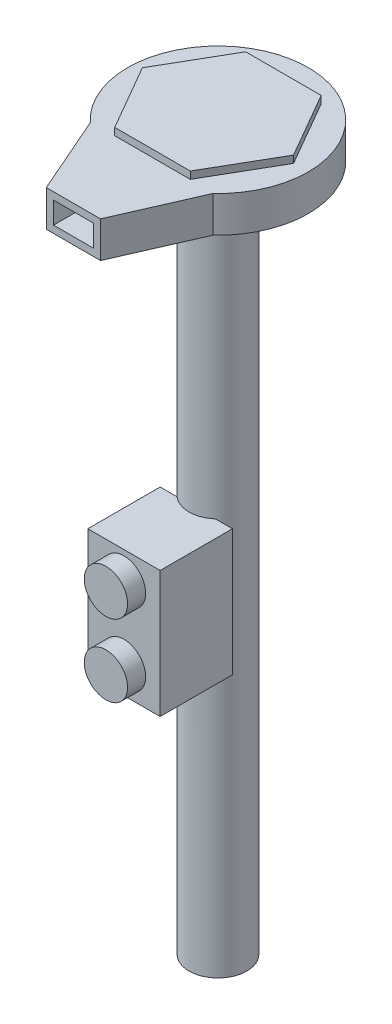
SolidWorks part; units mm, degrees
ref_plane "Front Plane" through (0, 0, 0) normal (0, 0, 1) x (1, 0, 0)
ref_plane "Top Plane" through (0, 0, 0) normal (0, 1, 0) x (1, 0, 0)
ref_plane "Right Plane" through (0, 0, 0) normal (1, 0, 0) x (0, 0, -1)
sketch "Sketch1" plane through (0, 0, 0) normal (0, 1, 0) x (1, 0, 0)
  circle A0 centre (0, 0) radius 4
  dimension "D1" = 8
extrude "Boss-Extrude1" add sketch "Sketch1" along normal blind 100 contours A0
sketch "Sketch2" plane through (0, 100, 0) normal (0, 1, 0) x (1, 0, 0)
  circle A0 centre (0, 0) radius 3
  dimension "D1" = 6
extrude "Cut-Extrude1" cut sketch "Sketch2" against normal through all
sketch "Sketch3" plane through (0, 100, 0) normal (0, 1, 0) x (1, 0, 0)
  circle A0 centre (0, 0) radius 12.5
  dimension "D1" = 25
extrude "Boss-Extrude2" add sketch "Sketch3" against normal blind 5
ref_plane "Plane1" through (0, 0, 20) normal (0, 0, 1) x (1, 0, 0)
sketch "Sketch4" plane through (0, 0, 20) normal (0, 0, 1) x (1, 0, 0)
  line L0 (12.5, 100) -> (-12.5, 100) construction
  line L1 (-3.75, 100) -> (3.75, 100)
  line L2 (-3.75, 100) -> (-3.75, 95)
  line L3 (-3.75, 95) -> (3.75, 95)
  line L4 (3.75, 100) -> (3.75, 95)
  line L5 (-4, 95) -> (4, 95) construction
  point P9 (0, 100)
  dimension "D1" = 0
  dimension "D2" = 7.5
  dimension "D3" = 5
sketch "Sketch5" plane through (0, 0, 0) normal (0, 0, 1) x (1, 0, 0)
  line L1 (-12.5, 100) -> (12.5, 100)
  line L2 (-12.5, 100) -> (-12.5, 95)
  line L3 (-12.5, 95) -> (12.5, 95)
  line L4 (12.5, 100) -> (12.5, 95)
loft "Loft2" add profiles "Sketch5", "Sketch4" connector at (-12.5, 100, 0) connector at (-3.75, 100, 20)
sketch "Sketch9" plane through (0, 0, 20) normal (0, 0, 1) x (1, 0, 0)
  line L0 (3.75, 100) -> (-3.75, 100) construction
  line L1 (-2.75, 99) -> (2.75, 99)
  line L2 (-2.75, 99) -> (-2.75, 96)
  line L3 (-2.75, 96) -> (2.75, 96)
  line L4 (2.75, 99) -> (2.75, 96)
  line L5 (-3.75, 100) -> (-3.75, 95) construction
  line L6 (3.75, 95) -> (3.75, 100) construction
  line L7 (-4, 95) -> (4, 95) construction
  point P4 (0, 99)
  dimension "D1" = 1
  dimension "D2" = 1
  dimension "D3" = 1
  dimension "D4" = 1
extrude "Cut-Extrude2" cut sketch "Sketch9" against normal blind 22.5
ref_plane "Plane2" through (0, 0, 3) normal (0, 0, 1) x (1, 0, 0)
extrude "Cut-Extrude3" cut sketch "Sketch2<2>" against normal through all
sketch "Sketch2<2>" plane through (0, 100, 0) normal (0, 1, 0) x (1, 0, 0) same geometry as "Sketch2"
sketch "Sketch14" plane through (0, 100, 0) normal (0, 1, 0) x (1, 0, 0)
  line L1 (10.4565, 0) -> (5.2283, 9.0556)
  line L2 (5.2283, 9.0556) -> (-5.2283, 9.0556)
  line L3 (-5.2283, 9.0556) -> (-10.4565, 0)
  line L4 (-10.4565, 0) -> (-5.2283, -9.0556)
  line L5 (-5.2283, -9.0556) -> (5.2283, -9.0556)
  line L6 (5.2283, -9.0556) -> (10.4565, 0)
  circle A0 centre (0, 0) radius 9.0556 construction
extrude "Boss-Extrude6" add sketch "Sketch14" along normal blind 1
sketch "Sketch18" plane through (0, 0, 3) normal (0, 0, 1) x (1, 0, 0)
  line L0 (-4, 95) -> (4, 95) construction
  line L1 (-5, 55) -> (5, 55)
  line L2 (-5, 55) -> (-5, 37.5)
  line L3 (-5, 37.5) -> (5, 37.5)
  line L4 (5, 55) -> (5, 37.5)
  point P4 (0, 55)
  dimension "D1" = 0
  dimension "D2" = 10
  dimension "D3" = 17.5
  dimension "D4" = 40
extrude "Boss-Extrude10" add sketch "Sketch18" along normal blind 10 contours L4 L3 L2 L1
sketch "Sketch19" plane through (0, 0, 13) normal (0, 0, 1) x (1, 0, 0)
  line L0 (-2.6458, 37.5) -> (2.6458, 37.5) construction
  line L1 (-5, 55) -> (5, 55) construction
  circle A0 centre (0, 51.25) radius 3
  circle A1 centre (0, 41.25) radius 3
  point P4 (0, 37.5)
  dimension "D2" = 6
  dimension "D4" = 6
  dimension "D1" = 0
  dimension "D3" = 3.75
  dimension "D5" = 10
extrude "Boss-Extrude11" add sketch "Sketch19" along normal blind 2.5
